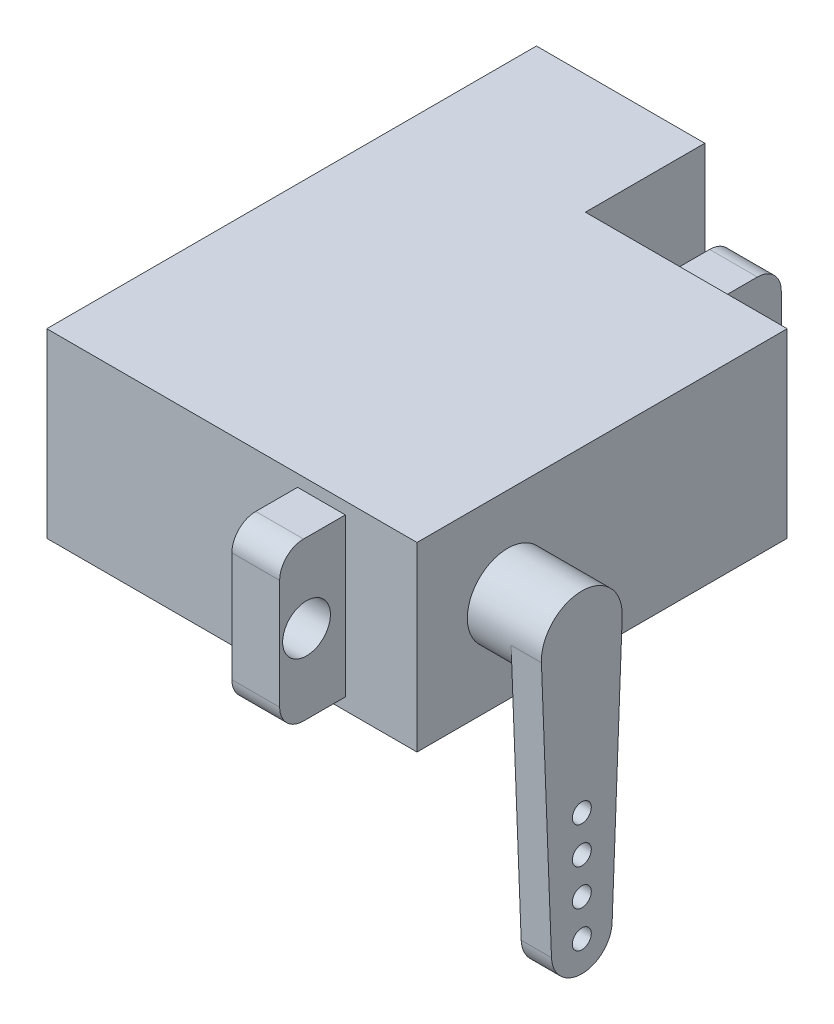
SolidWorks part; units mm, degrees
note: '?' marks a value the reader was unsure of.
ref_plane "XY" through (0, 0, 0) normal (0, 0, 1) x (1, 0, 0)
ref_plane "XZ" through (0, 0, 0) normal (0, 1, 0) x (1, 0, 0)
ref_plane "YZ" through (0, 0, 0) normal (1, 0, 0) x (0, 0, -1)
ref_axis "X" through (-1.86, 0, 0) along (1, 0, 0)?
ref_axis "Y" through (0, -25.9832, 0) along (0, 1, 0)?
ref_axis "Z" through (0, 0, 35.525) along (0, 0, -1)?
sketch "Sketch1" plane through (0, 0, 0) normal (1, 0, 0) x (0, 0, -1)
  line L1 (-15.5, -7.6) -> (15.5, -7.6)
  line L2 (-15.5, -7.6) -> (-15.5, 7.6)
  line L3 (-15.5, 7.6) -> (15.5, 7.6)
  line L4 (15.5, -7.6) -> (15.5, 7.6)
  line L5 (-15.5, -7.6) -> (15.5, 7.6) construction
  line L6 (-15.5, 7.6) -> (15.5, -7.6) construction
  point P0 (0, 0)
  dimension "D1" = 15.2
  dimension "D2" = 31
extrude "Boss-Extrude1" add sketch "Sketch1" along normal blind 31
sketch "Sketch2" plane through (0, 0, 0) normal (1, 0, 0) x (0, 0, -1)
  line L0 (-15.5, 0) -> (0, 0) construction
  line L1 (-15.5, 6.6) -> (-19, 6.6)
  line L2 (-15.5, 6.6) -> (-15.5, -6.6)
  line L3 (-15.5, -6.6) -> (-19, -6.6)
  line L4 (-21, 4.6) -> (-21, -4.6)
  line L5 (15.5, -6.6) -> (19, -6.6)
  line L6 (15.5, -6.6) -> (15.5, 6.6)
  line L7 (15.5, 6.6) -> (19, 6.6)
  line L8 (21, -4.6) -> (21, 4.6)
  line L9 (15.5, 7.6) -> (-15.5, 7.6) construction
  line L10 (-15.5, 7.6) -> (-15.5, -7.6) construction
  line L11 (15.5, -7.6) -> (15.5, 7.6) construction
  arc A0 (19, 6.6) -> (21, 4.6) centre (19, 4.6) cw
  arc A1 (19, -6.6) -> (21, -4.6) centre (19, -4.6) ccw
  arc A2 (-19, -6.6) -> (-21, -4.6) centre (-19, -4.6) cw
  arc A3 (-19, 6.6) -> (-21, 4.6) centre (-19, 4.6) ccw
  dimension "D3" = 2
  dimension "D1" = 42
  dimension "D2" = 1
extrude "Boss-Extrude2" add sketch "Sketch2" along normal blind 4 from offset 21
hole_wizard "Ø4.0mm Dowel Hole1" positions "Sketch5" profile "Sketch4" hole size "Ø4.0" standard "ANSI Metric"
sketch "Sketch5" plane through (25, 0, 0) normal (1, 0, 0) x (0, 0, -1)
  line L0 (-18.75, 0) -> (18.75, 0) construction
  point P0 (-18.75, 0)
  point P2 (18.75, 0)
  point P26 (0, 0)
  dimension "D1" = 37.5
sketch "Sketch4" plane through (25, 0, 18.75) normal (0, 1, 0) x (0, 0, -1)
  line L0 (0, 0) -> (0, 11.8697)
  line L1 (0, 11.8697) -> (2, 10.668)
  line L2 (2, 10.668) -> (2, 0)
  line L5 (2, 0) -> (0, 0)
  line L10 (0, 11.8697) -> (-2, 10.668) construction
  line L11 (0, -6.35) -> (0, 107.95) construction
  dimension "Hole Dia." = 4
  dimension "Hole Depth" = 10.668
  dimension "Drill Angle" = 118
sketch "Sketch6" plane through (31, 0, 0) normal (1, 0, 0) x (0, 0, -1)
  line L0 (-7.9, 0) -> (-15.5, 0) construction
  line L1 (-15.5, 7.6) -> (-15.5, -7.6) construction
  circle A0 centre (-7.9, 0) radius 3.3841
  dimension "D1" = 7.6
extrude "Boss-Extrude3" add sketch "Sketch6" along normal blind 6.2
sketch "Sketch7" plane through (37.2, 0, 0) normal (1, 0, 0) x (0, 0, -1)
  line L0 (-4.5184, -0.1308) -> (-5.3619, -21.9422)
  line L1 (-10.4381, -21.9422) -> (-11.2816, -0.1308)
  line L2 (-7.9, 0) -> (-7.9, -21.844) construction
  arc A0 (-11.2816, -0.1308) -> (-4.5184, -0.1308) centre (-7.9, 0) cw
  circle A1 centre (-7.9, 0) radius 3.3841 construction
  arc A2 (-5.3619, -21.9422) -> (-10.4381, -21.9422) centre (-7.9, -21.844) cw
  dimension "D2" = 2.54
  dimension "D1" = 21.844
extrude "Boss-Extrude4" add sketch "Sketch7" against normal blind 2.54
hole_wizard "1/16 (0.0625) Diameter Hole1" positions "Sketch10" profile "Sketch11" hole size "1/16" standard "ANSI Inch" end condition up to next
sketch "Sketch10" plane through (37.2, 0, 0) normal (1, 0, 0) x (0, 0, -1)
  line L0 (-7.9, 0) -> (-7.9, -12.7)
  line L1 (-7.9, -12.7) -> (-7.9, -15.748)
  line L2 (-7.9, -15.748) -> (-7.9, -18.796)
  line L3 (-7.9, -18.796) -> (-7.9, -21.844)
  point P0 (-7.9, -12.7)
  point P2 (-7.9, -15.748)
  point P4 (-7.9, -18.796)
  point P6 (-7.9, -21.844)
  dimension "D1" = 3.048
  dimension "D2" = 12.7
sketch "Sketch11" plane through (37.2, -12.7, 7.9) normal (0, 1, 0) x (0, 0, -1)
  line L0 (0, 0) -> (0, 2.54)
  line L1 (0, 2.54) -> (0.7937, 2.54)
  line L2 (0.7937, 2.54) -> (0.7937, 0)
  line L5 (0.7937, 0) -> (0, 0)
  line L11 (0, -6.35) -> (0, 107.95) construction
  dimension "Thru Hole Dia." = 1.5875
  dimension "Thru Hole Depth" = 2.54
sketch "Sketch12" plane through (0, 0, -15.5) normal (0, 0, -1) x (-1, 0, 0)
  line L0 (-31, -7.6) -> (0, -7.6) construction
  line L1 (0, -7.6) -> (-14.1, -7.6)
  line L2 (0, -7.6) -> (0, 7.6)
  line L3 (0, 7.6) -> (-14.1, 7.6)
  line L4 (-14.1, -7.6) -> (-14.1, 7.6)
  line L5 (-31, 7.6) -> (0, 7.6) construction
  line L6 (-21, 6.6) -> (-21, -6.6) construction
  line L7 (0, -7.6) -> (0, 7.6) construction
  dimension "D1" = 6.9
extrude "Boss-Extrude5" add sketch "Sketch12" along normal blind 10
